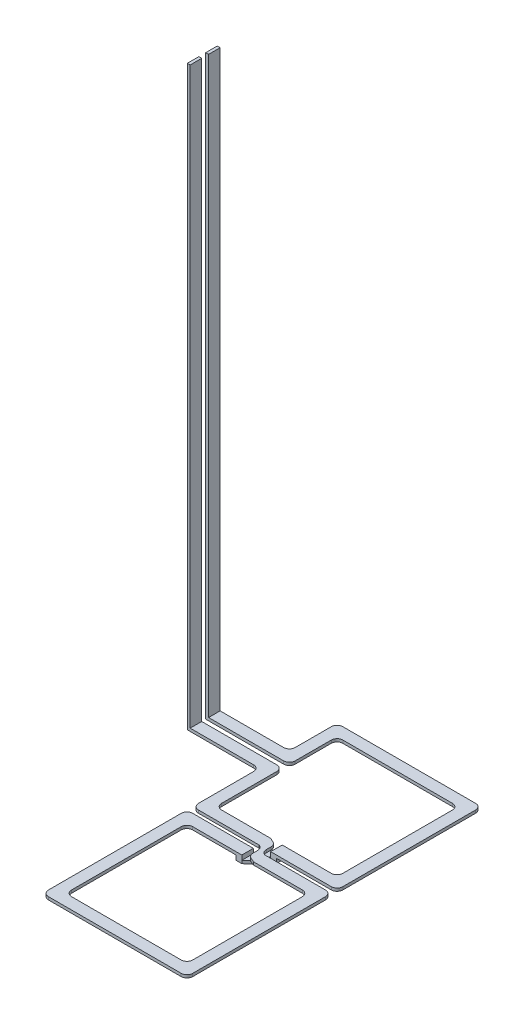
SolidWorks part; units mm, degrees
ref_plane "前视基准面" through (0, 0, 0) normal (0, 0, 1) x (1, 0, 0)
ref_plane "上视基准面" through (0, 0, 0) normal (0, 1, 0) x (1, 0, 0)
ref_plane "右视基准面" through (0, 0, 0) normal (1, 0, 0) x (0, 0, -1)
sketch "草图1" plane through (0, 0, 0) normal (0, 1, 0) x (1, 0, 0)
  line L0 (-9.5, 23.5) -> (9.5, 23.5)
  line L1 (-11.5, 0.5) -> (11.5, 0.5)
  line L2 (-12.5, 1.5) -> (-12.5, 11.0583)
  line L3 (-11.5, 25.5) -> (11.5, 25.5)
  line L4 (12.5, 1.5) -> (12.5, 24.5)
  line L5 (-12.5, 0.5) -> (12.5, 25.5) construction
  line L6 (-12.5, 25.5) -> (12.5, 0.5) construction
  line L7 (10.5, 3.5) -> (10.5, 22.5)
  line L8 (-9.5, 2.5) -> (9.5, 2.5)
  line L9 (-10.5, 3.5) -> (-10.5, 13.0583)
  line L10 (-10.5, 2.5) -> (-10.5, 23.5) construction
  line L11 (-10.5, 23.5) -> (10.5, 23.5) construction
  line L12 (-12.5, 0.5) -> (-12.5, 25.5) construction
  line L13 (-12.5, 25.5) -> (12.5, 25.5) construction
  line L14 (12.5, 0.5) -> (12.5, 25.5) construction
  line L15 (10.5, 2.5) -> (10.5, 23.5) construction
  line L16 (-12.5, 0.5) -> (12.5, 0.5) construction
  line L17 (-10.5, 2.5) -> (10.5, 2.5) construction
  line L18 (-11.5, 15.2464) -> (-25, 15.2464)
  line L19 (-25, 17.2464) -> (-25, 15.2464)
  line L20 (-11.5, 14.0583) -> (-25, 14.0583)
  line L21 (-12.5, 18.2464) -> (-12.5, 24.5)
  line L22 (-10.5, 16.2464) -> (-10.5, 22.5)
  line L23 (-13.5, 17.2464) -> (-25, 17.2464)
  line L24 (-13.5, 12.0583) -> (-25, 12.0583)
  line L25 (-25, 12.0583) -> (-25, 14.0583)
  line L26 (0, 0) -> (15.2827, 0) construction
  line L27 (-11.5, -0.5) -> (11.5, -0.5)
  line L28 (-12.5, -25.5) -> (12.5, -0.5) construction
  line L29 (-12.5, -0.5) -> (12.5, -25.5) construction
  line L30 (-9.5, -2.5) -> (9.5, -2.5)
  line L31 (10.5, -3.5) -> (10.5, -22.5)
  line L32 (12.5, -1.5) -> (12.5, -24.5)
  line L33 (-11.5, -25.5) -> (11.5, -25.5)
  line L34 (-9.5, -23.5) -> (9.5, -23.5)
  line L35 (-12.5, -1.5) -> (-12.5, -24.5)
  line L36 (-10.5, -3.5) -> (-10.5, -22.5)
  arc A0 (-10.5, 22.5) -> (-9.5, 23.5) centre (-9.5, 22.5) cw
  arc A1 (-12.5, 24.5) -> (-11.5, 25.5) centre (-11.5, 24.5) cw
  arc A2 (12.5, 24.5) -> (11.5, 25.5) centre (11.5, 24.5) ccw
  arc A3 (10.5, 22.5) -> (9.5, 23.5) centre (9.5, 22.5) ccw
  arc A4 (-11.5, 0.5) -> (-12.5, 1.5) centre (-11.5, 1.5) cw
  arc A5 (-9.5, 2.5) -> (-10.5, 3.5) centre (-9.5, 3.5) cw
  arc A6 (9.5, 2.5) -> (10.5, 3.5) centre (9.5, 3.5) ccw
  arc A7 (11.5, 0.5) -> (12.5, 1.5) centre (11.5, 1.5) ccw
  arc A8 (-12.5, 18.2464) -> (-13.5, 17.2464) centre (-13.5, 18.2464) cw
  arc A9 (-10.5, 16.2464) -> (-11.5, 15.2464) centre (-11.5, 16.2464) cw
  arc A10 (-10.5, 13.0583) -> (-11.5, 14.0583) centre (-11.5, 13.0583) ccw
  arc A11 (-13.5, 12.0583) -> (-12.5, 11.0583) centre (-13.5, 11.0583) cw
  arc A12 (-10.5, -22.5) -> (-9.5, -23.5) centre (-9.5, -22.5) ccw
  arc A13 (-12.5, -24.5) -> (-11.5, -25.5) centre (-11.5, -24.5) ccw
  arc A14 (-11.5, -0.5) -> (-12.5, -1.5) centre (-11.5, -1.5) ccw
  arc A15 (-9.5, -2.5) -> (-10.5, -3.5) centre (-9.5, -3.5) ccw
  arc A16 (11.5, -0.5) -> (12.5, -1.5) centre (11.5, -1.5) cw
  arc A17 (9.5, -2.5) -> (10.5, -3.5) centre (9.5, -3.5) cw
  arc A18 (10.5, -22.5) -> (9.5, -23.5) centre (9.5, -22.5) cw
  arc A19 (12.5, -24.5) -> (11.5, -25.5) centre (11.5, -24.5) cw
  point P0 (0, 13)
  point P46 (-10.5, 15.2464)
  point P81 (0, -13)
  dimension "D4" = 1
  dimension "D5" = 1
  dimension "D6" = 1
  dimension "D7" = 1
  dimension "D10" = 1
  dimension "D11" = 1
  dimension "D12" = 1
  dimension "D13" = 1
  dimension "D1" = 25
  dimension "D2" = 13
  dimension "D8" = 2
  dimension "D9" = 2
  dimension "D14" = 25
  dimension "D3" = 2
ref_axis "基准轴2" through (0, 0, 0) along (1, 0, 0)
ref_axis "基准轴1" through (0, 0, 0) along (0, 1, 0)
extrude "凸台-拉伸1" add sketch "草图1" along normal blind 0.5
sketch "草图2" plane through (0, 0, 0) normal (0, 1, 0) x (1, 0, 0)
  line L1 (-1, -4.5057) -> (1, -4.5057)
  line L2 (-1, -4.5057) -> (-1, 4.5057)
  line L3 (-1, 4.5057) -> (1, 4.5057)
  line L4 (1, -4.5057) -> (1, 4.5057)
  line L5 (-1, -4.5057) -> (1, 4.5057) construction
  line L6 (-1, 4.5057) -> (1, -4.5057) construction
  point P0 (0, 0)
  dimension "D1" = 2
extrude "切除-拉伸1" cut sketch "草图2" against normal blind 10 and the other way blind 10
sketch "草图3" plane through (0, 0, 0) normal (0, 1, 0) x (1, 0, 0)
  line L0 (-1, 2.5) -> (-0.2838, 2.1763)
  line L1 (0.3043, 1.265) -> (0.3043, 0.4599)
  line L2 (0.8924, -0.4514) -> (1, -0.5)
  line L3 (0.2838, -2.1763) -> (1, -2.5)
  line L4 (-1, 0.5) -> (-0.8924, 0.4514)
  line L5 (-0.3043, -0.4599) -> (-0.3043, -1.265)
  line L7 (-1, 2.5) -> (-1, 0.5)
  line L8 (1, -0.5) -> (1, -2.5)
  arc A0 (-0.2838, 2.1763) -> (0.3043, 1.265) centre (-0.6957, 1.265) cw
  arc A1 (0.3043, 0.4599) -> (0.8924, -0.4514) centre (1.3043, 0.4599) ccw
  arc A2 (-0.3043, -1.265) -> (0.2838, -2.1763) centre (0.6957, -1.265) ccw
  arc A3 (-0.3043, -0.4599) -> (-0.8924, 0.4514) centre (-1.3043, -0.4599) ccw
  dimension "D1" = 1
extrude "凸台-拉伸2" add sketch "草图3" along normal blind 0.5
sketch "草图4" plane through (0, 0, 0) normal (0, 1, 0) x (1, 0, 0)
  line L0 (-1, -2.5) -> (-9.5, -2.5) construction
  line L1 (-1, -0.5) -> (-2, -0.5)
  line L2 (-1, -0.5) -> (-1, -2.5)
  line L3 (-1, -2.5) -> (-2, -2.5)
  line L4 (-2, -0.5) -> (-2, -2.5)
  line L5 (1, 0.5) -> (11.5, 0.5) construction
  line L6 (1, 2.5) -> (2, 2.5)
  line L7 (1, 2.5) -> (1, 0.5)
  line L8 (1, 0.5) -> (2, 0.5)
  line L9 (2, 2.5) -> (2, 0.5)
  dimension "D1" = 1
extrude "凸台-拉伸3" add sketch "草图4" against normal blind 0.8
ref_plane "基准面2" through (0, -0.8, 0) normal (0, 1, 0) x (1, 0, 0)
sketch "草图5" plane through (0, -0.8, 0) normal (0, 1, 0) x (1, 0, 0)
  line L0 (-1, -2.5) -> (0.0838, -1.5946)
  line L1 (0.4427, -0.8271) -> (0.4427, -0.4332)
  line L2 (0.8016, 0.3343) -> (1, 0.5)
  line L3 (1, 2.5) -> (-0.0838, 1.5946)
  line L4 (-0.4427, 0.8271) -> (-0.4427, 0.4332)
  line L5 (-0.8016, -0.3343) -> (-1, -0.5)
  line L6 (-1, -2.5) -> (-1, -0.5)
  line L7 (1, 0.5) -> (1, 2.5)
  arc A0 (0.4427, -0.8271) -> (0.0838, -1.5946) centre (-0.5573, -0.8271) cw
  arc A1 (0.8016, 0.3343) -> (0.4427, -0.4332) centre (1.4427, -0.4332) ccw
  arc A2 (-0.4427, 0.8271) -> (-0.0838, 1.5946) centre (0.5573, 0.8271) cw
  arc A3 (-0.4427, 0.4332) -> (-0.8016, -0.3343) centre (-1.4427, 0.4332) cw
  dimension "D1" = 1
extrude "凸台-拉伸4" add sketch "草图5" along normal blind 0.5
sketch "草图6" plane through (0, 0, 0) normal (0, 1, 0) x (1, 0, 0)
  line L0 (-25, 15.2464) -> (-11.5, 15.2464) construction
  line L1 (-25, 17.2464) -> (-24.5, 17.2464)
  line L2 (-25, 17.2464) -> (-25, 15.2464)
  line L3 (-25, 15.2464) -> (-24.5, 15.2464)
  line L4 (-24.5, 17.2464) -> (-24.5, 15.2464)
  line L5 (-25, 12.0583) -> (-13.5, 12.0583) construction
  line L6 (-25, 14.0583) -> (-24.5, 14.0583)
  line L7 (-25, 14.0583) -> (-25, 12.0583)
  line L8 (-25, 12.0583) -> (-24.5, 12.0583)
  line L9 (-24.5, 14.0583) -> (-24.5, 12.0583)
  dimension "D1" = 0.5
extrude "凸台-拉伸5" add sketch "草图6" along normal blind 100
